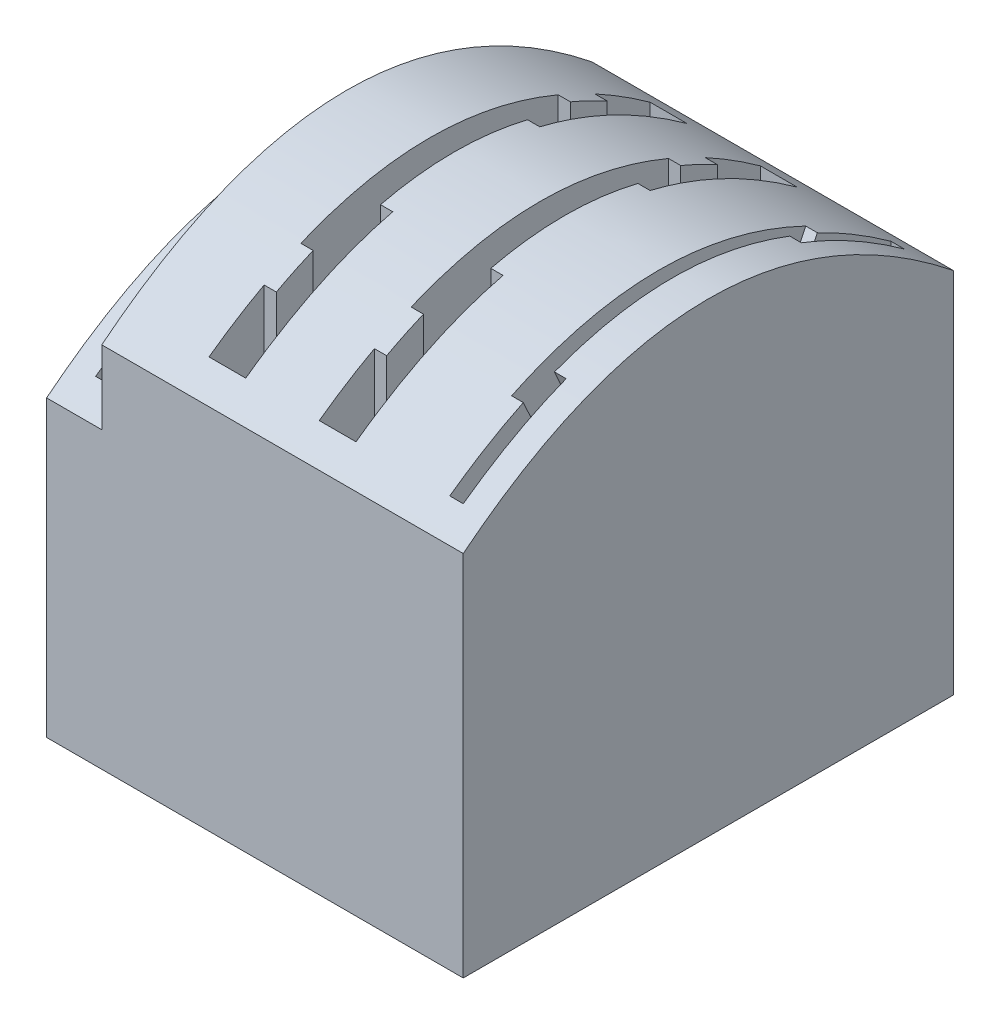
SolidWorks part; units mm, degrees
ref_plane "Front Plane" through (0, 0, 0) normal (0, 0, 1) x (1, 0, 0)
ref_plane "Top Plane" through (0, 0, 0) normal (0, 1, 0) x (1, 0, 0)
ref_plane "Right Plane" through (0, 0, 0) normal (1, 0, 0) x (0, 0, -1)
sketch "Sketch1" plane through (0, 0, 0) normal (1, 0, 0) x (0, 0, -1)
  line L2 (-100, 85) -> (-100, -65)
  line L3 (-100, -65) -> (100, -65)
  line L4 (100, 85) -> (100, -65)
  spline S0 degree 2 poles (-100, 85) (0, 165) (100, 85) knots 0 0 0 1 1 1
  point P4 (-100, 85)
  point P5 (100, 85)
  dimension "D1" = 200
  dimension "D2" = 100
  dimension "D3" = 150
  dimension "D4" = 150
  dimension "D5" = 40
  dimension "D6" = 100
  dimension "D7" = 125
extrude "Base" add sketch "Sketch1" along normal blind 170
ref_plane "New Top" through (0, 125, 0) normal (0, 1, 0) x (1, 0, 0)
sketch "Sketch3" plane through (0, 125, 0) normal (0, 1, 0) x (1, 0, 0)
  line L0 (170, -100) -> (170, 100) construction
  line L1 (116.25, 90) -> (101.25, 90)
  line L2 (116.25, 90) -> (116.25, 30)
  line L3 (116.25, -90) -> (101.25, -90)
  line L4 (101.25, 90) -> (101.25, 67.5)
  line L5 (86.25, -104.5688) -> (86.25, 145.9081) construction
  line L6 (101.25, 52.5) -> (106.25, 52.5)
  line L7 (170, 100) -> (0, 100) construction
  line L12 (170, -100) -> (0, -100) construction
  line L14 (101.25, 67.5) -> (106.25, 67.5)
  line L15 (106.25, 52.5) -> (106.25, 67.5)
  line L16 (116.25, 30) -> (111.25, 30)
  line L18 (116.25, -30) -> (111.25, -30)
  line L19 (111.25, 30) -> (111.25, -30)
  line L20 (101.25, -67.5) -> (106.25, -67.5)
  line L22 (101.25, -52.5) -> (106.25, -52.5)
  line L23 (106.25, -67.5) -> (106.25, -52.5)
  line L24 (71.25, 90) -> (56.25, 90)
  line L25 (71.25, 90) -> (71.25, 30)
  line L26 (71.25, -90) -> (56.25, -90)
  line L27 (56.25, 90) -> (56.25, 67.5)
  line L28 (56.25, 52.5) -> (61.25, 52.5)
  line L30 (56.25, 67.5) -> (61.25, 67.5)
  line L31 (61.25, 52.5) -> (61.25, 67.5)
  line L32 (71.25, 30) -> (66.25, 30)
  line L34 (71.25, -30) -> (66.25, -30)
  line L35 (66.25, 30) -> (66.25, -30)
  line L36 (56.25, -67.5) -> (61.25, -67.5)
  line L38 (56.25, -52.5) -> (61.25, -52.5)
  line L39 (61.25, -67.5) -> (61.25, -52.5)
  line L40 (116.25, -30) -> (116.25, -90)
  line L41 (71.25, -30) -> (71.25, -90)
  line L42 (56.25, 52.5) -> (56.25, -52.5)
  line L45 (56.25, -67.5) -> (56.25, -90)
  line L46 (101.25, -67.5) -> (101.25, -90)
  line L47 (101.25, 52.5) -> (101.25, -52.5)
  dimension "D1" = 53.75
  dimension "D2" = 15
  dimension "D3" = 15
  dimension "D4" = 2
  dimension "D5" = 15
  dimension "10" = 10
  dimension "D8" = 10
  dimension "D9" = 22.5
  dimension "D10" = 15
  dimension "D11" = 5
  dimension "D12" = 5
  dimension "D13" = 22.5
  dimension "D14" = 22.5
  dimension "D15" = 22.5
  dimension "D16" = 15
  dimension "D17" = 5
sketch "Sketch4" plane through (0, 125, 0) normal (0, 1, 0) x (1, 0, 0)
  line L1 (22.5, 87.5) -> (10, 87.5)
  line L2 (22.5, 87.5) -> (22.5, -87.5)
  line L3 (22.5, -87.5) -> (10, -87.5)
  line L4 (10, 87.5) -> (10, -87.5)
  line L5 (170, 100) -> (0, 100) construction
  line L6 (170, -100) -> (0, -100) construction
  line L7 (0, 100) -> (0, -100) construction
  dimension "D1" = 10
  dimension "D2" = 12.5
  dimension "D3" = 12.5
  dimension "D4" = 12.5
sketch "Sketch5" plane through (0, 125, 0) normal (0, 1, 0) x (1, 0, 0)
  line L0 (170, -100) -> (170, 100) construction
  line L1 (160, 90) -> (154.5, 90)
  line L2 (160, 90) -> (160, 48)
  line L3 (160, -90) -> (154.5, -90)
  line L4 (149.75, 60) -> (149.75, -60)
  line L5 (170, 100) -> (0, 100) construction
  line L6 (170, -100) -> (0, -100) construction
  line L7 (160, -48) -> (160, -90)
  line L10 (149.75, 60) -> (154.5, 60)
  line L11 (154.5, 90) -> (154.5, 60)
  line L12 (160, 48) -> (155.25, 48)
  line L14 (160, -48) -> (155.25, -48)
  line L15 (155.25, 48) -> (155.25, -48)
  line L18 (149.75, -60) -> (154.5, -60)
  line L19 (154.5, -90) -> (154.5, -60)
  dimension "D1" = 5.5
  dimension "D3" = 10
  dimension "D4" = 10
  dimension "D5" = 10
  dimension "D6" = 30
  dimension "D7" = 30
  dimension "D8" = 5.5
  dimension "D9" = 12
  dimension "D10" = 12
  dimension "D11" = 5.5
extrude "Flaps Cut" cut sketch "Sketch5" against normal up to surface (190 mm away) up to face at (85, -65, 0)
extrude "Throttle Cut" cut sketch "Sketch3" against normal up to surface (190 mm away) up to face at (155.6667, -65, 0)
extrude "Wing Sweep Cut" cut sketch "Sketch4" against normal up to surface (190 mm away) up to face at (107.5, -65, 0)
sketch "Sketch7" plane through (0, -65, 0) normal (0, -1, 0) x (1, 0, 0)
  line L0 (170, 100) -> (0, 100) construction
  line L1 (10, 90) -> (160, 90)
  line L2 (10, 90) -> (10, -90)
  line L3 (10, -90) -> (160, -90)
  line L4 (160, 90) -> (160, -90)
  dimension "D1" = 10
extrude "Bottom Cut" cut sketch "Sketch7" against normal blind 140
sketch "Sketch20" plane through (155.25, 0, 0) normal (-1, 0, 0) x (0, 0, 1)
  line L0 (48, 115.784) -> (25.5, 65.784)
  line L1 (25.5, 65.784) -> (48, 65.784)
  line L2 (48, 65.784) -> (48, 115.784)
  line L3 (-48, 115.784) -> (-48, 65.784)
  line L4 (-48, 65.784) -> (-24.5, 65.784)
  line L5 (-24.5, 65.784) -> (-48, 115.784)
  dimension "D1" = 90
  dimension "D2" = 22.5
  dimension "D3" = 50
  dimension "D4" = 50
  dimension "D5" = 23.5
extrude "Cut-Extrude10" cut sketch "Sketch20" against normal blind 4.75
sketch "Sketch22" plane through (160, 0, 0) normal (-1, 0, 0) x (0, 0, 1)
  line L0 (-60, 110.6) -> (-43, 75)
  line L2 (-43, 75) -> (-60, 75)
  line L3 (-60, 75) -> (-60, 110.6)
  line L4 (-60, 75) -> (-60, 110.6) construction
  line L5 (60, 110.6) -> (60, 75)
  line L11 (60, 75) -> (43.75, 75)
  line L12 (43.75, 75) -> (60, 110.6)
  line L13 (-90, 75) -> (-60, 75) construction
  line L14 (60, 75) -> (90, 75) construction
  dimension "D1" = 0
  dimension "D2" = 17
  dimension "D3" = 90
  dimension "D4" = 0
  dimension "D5" = 16.25
  dimension "D6" = 0
  dimension "D7" = 0
  dimension "D8" = 0
extrude "Boss-Extrude5" add sketch "Sketch22" against normal blind 4.75 from surface starting at face at (149.75, 92.8, 15)
sketch "Sketch9" plane through (0, 0, 0) normal (-1, 0, 0) x (0, 0, 1)
  line L0 (100, 85) -> (100, -65) construction
  line L1 (-100, 55) -> (-100, 135)
  line L2 (-100, 135) -> (100, 135)
  line L3 (100, 135) -> (100, 55)
  spline S0 degree 2 poles (-100, 55) (0, 135) (100, 55) knots 0 0 0 1 1 1
  dimension "D1" = 100
  dimension "D2" = 40
  dimension "D3" = 100
  dimension "D4" = 40
  dimension "D5" = 0
  dimension "D6" = 30
  dimension "D7" = 80
extrude "Cut-Extrude4" cut sketch "Sketch9" against normal up to surface (22.5 mm away) up to face at (22.5, 84.6875, -21.875)
sketch "Sketch13" plane through (0, 75, 0) normal (0, -1, 0) x (1, 0, 0)
  line L0 (56.25, 90) -> (22.5, 90) construction
  line L1 (22.5, 90) -> (32.5, 90)
  line L2 (22.5, 90) -> (22.5, -90)
  line L3 (22.5, -90) -> (32.5, -90)
  line L4 (32.5, 90) -> (32.5, -90)
  line L5 (22.5, -90) -> (56.25, -90) construction
  dimension "D1" = 10
  dimension "D2" = 0
  dimension "D3" = 0
extrude "Boss-Extrude2" add sketch "Sketch13" along normal blind 140
sketch "Sketch12" plane through (22.5, 0, 0) normal (-1, 0, 0) x (0, 0, 1)
  line L0 (-48.4309, 58.2758) -> (-48.4309, 55.2758)
  line L1 (100, 27.75) -> (100, 24.75)
  spline S0 degree 3 poles (-48.4309, 58.2758) (3.558, 77.5898) (53.0349, 67.4145) (100, 27.75) knots 0.031016 0.031016 0.031016 0.031016 1 1 1 1
  spline S1 degree 3 poles (100, 24.75) (53.0349, 64.4145) (3.558, 74.5898) (-48.4309, 55.2758) knots 0 0 0 0 0.968984 0.968984 0.968984 0.968984
  point P0 (0, 64.75)
  point P2 (100, 24.75)
  point P4 (0, 67.75)
  point P5 (-100, 23.75)
  point P6 (100, 27.75)
  dimension "D1" = 100
  dimension "D4" = 40
  dimension "D5" = 40
  dimension "D6" = 100
  dimension "D8" = 27.25
  dimension "D9" = 3
extrude "Boss-Extrude1" add sketch "Sketch12" along normal blind 2.5
sketch "Sketch17" plane through (22.5, 0, 0) normal (-1, 0, 0) x (0, 0, 1)
  line L0 (-49.7797, 57.8455) -> (-56.5642, 70.771)
  line L1 (-56.5642, 70.771) -> (-59.2205, 69.3767)
  line L2 (-59.2205, 69.3767) -> (-51.0872, 53.8816)
  line L3 (-51.0872, 53.8816) -> (-48.4309, 55.2758)
  line L5 (-48.4309, 58.2758) -> (-49.7797, 57.8455)
  line L6 (-48.4309, 58.2758) -> (-48.4309, 55.2758)
  dimension "D1" = 90
  dimension "25" = 17.5
  dimension "D2" = 3
  dimension "D3" = 90
  dimension "D4" = 90
  dimension "D5" = 100
extrude "Boss-Extrude3" add sketch "Sketch17" along normal blind 2.5
sketch "Sketch19" plane through (22.5, 0, 0) normal (-1, 0, 0) x (0, 0, 1)
  line L0 (-100, -65) -> (-100, 55) construction
  line L1 (-55.7563, 69.232) -> (-56.9133, 71.6936)
  line L2 (-49.7797, 57.8455) -> (-56.5642, 70.771) construction
  line L3 (-100, 45.5) -> (-100, 42.5)
  spline S0 degree 2 poles (-100, 42.5) (-76.9596, 59.4626) (-55.7563, 69.232) knots 0 0 0 0.212033 0.212033 0.212033
  spline S1 degree 2 poles (-100, 45.5) (-77.5381, 61.9998) (-56.9133, 71.6936) knots 0 0 0 0.206248 0.206248 0.206248
  dimension "D6" = 12.5
  dimension "D4" = 26.732
  dimension "D3" = 2.7199
  dimension "D5" = 0
  dimension "D11" = 0
  dimension "D12" = 3
extrude "Boss-Extrude4" add sketch "Sketch19" along normal blind 2.5
fillet "Fillet1" radius 2.5 4 edges at (21.25, 53.8816, -51.0872) (21.25, 57.8455, -49.7797) (21.25, 67.954, -58.4737) (21.25, 71.6936, -56.9133)
sketch "Sketch23" plane through (170, 0, 0) normal (1, 0, 0) x (0, 0, -1)
  circle A0 centre (0, 0) radius 9.5
  circle A1 centre (0, 0) radius 6
  dimension "D1" = 19
  dimension "D2" = 12
extrude "Boss-Extrude6" add sketch "Sketch23" against normal blind 5 from surface starting at face at (160, 54.596, -5.148)
